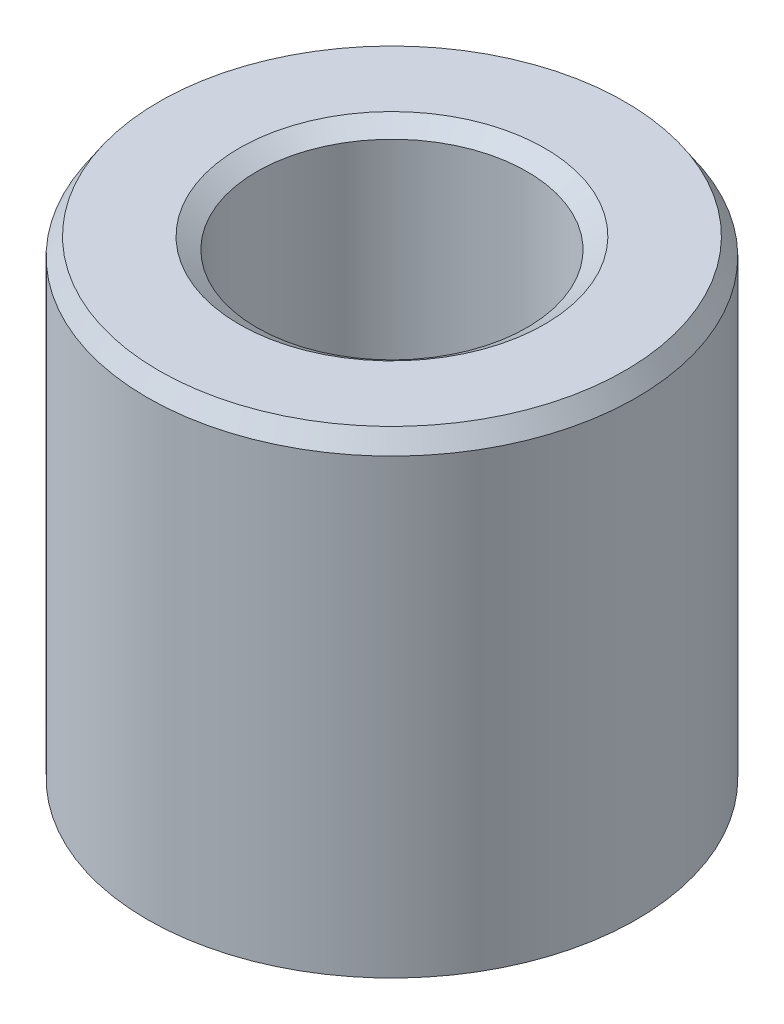
SolidWorks part; units mm, degrees
ref_plane "Front Plane" through (0, 0, 0) normal (0, 0, 1) x (1, 0, 0)
ref_plane "Top Plane" through (0, 0, 0) normal (0, 1, 0) x (1, 0, 0)
ref_plane "Right Plane" through (0, 0, 0) normal (1, 0, 0) x (0, 0, -1)
sketch "Sketch1" plane through (0, 0, 0) normal (0, 1, 0) x (1, 0, 0)
  circle A0 centre (0, 0) radius 45
  dimension "SLEEVE_OD" = 90
extrude "Boss-Extrude1" add sketch "Sketch1" along normal blind 88.5319
sketch "Sketch2" plane through (0, 0, 0) normal (0, 1, 0) x (1, 0, 0)
  circle A0 centre (0, 0) radius 24.8697
  dimension "BORE_D" = 49.7393
extrude "Cut-Extrude1" cut sketch "Sketch2" along normal through all
chamfer "Chamfer1" distance 3.2283 angle 33.418 4 edges at (0, 88.5319, 24.8697) (0, 0, 24.8697) (0, 0, 45) (0, 88.5319, 45) first distance on face at (0, 88.5319, 24.8697) first distance on face at (0, 0, 24.8697) first distance on face at (0, 88.5319, 45)
